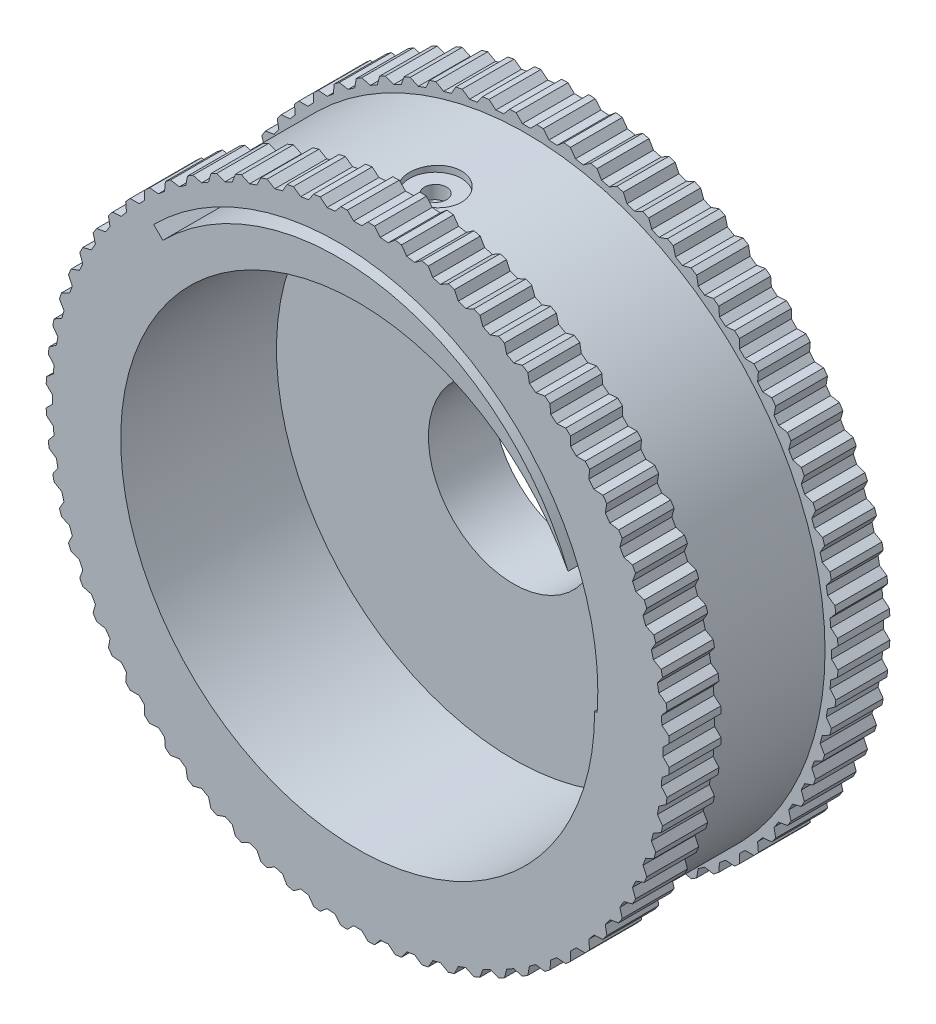
SolidWorks part; units mm, degrees
ref_plane "Front Plane" through (0, 0, 0) normal (0, 0, 1) x (1, 0, 0)
ref_plane "Top Plane" through (0, 0, 0) normal (0, 1, 0) x (1, 0, 0)
ref_plane "Right Plane" through (0, 0, 0) normal (1, 0, 0) x (0, 0, -1)
sketch "Sketch1" plane through (0, 0, 0) normal (0, 0, 1) x (1, 0, 0)
  circle A0 centre (0, 0) radius 24
  circle A1 centre (0, 0) radius 6.55
  dimension "D1" = 48
  dimension "D2" = 13.1
extrude "Main" add sketch "Sketch1" along normal mid plane 17
sketch "Sketch2" plane through (0, 0, 8.5) normal (0, 0, 1) x (1, 0, 0)
  circle A0 centre (0, 0) radius 18.25
  dimension "D1" = 36.5
extrude "ForSpringHole" cut sketch "Sketch2" against normal blind 12
ref_axis "Axis1" through (0, 0, 18.9) along (0, 0, -1)
sketch "Sketch3" plane through (0, 0, 8.5) normal (0, 0, 1) x (1, 0, 0)
  line L1 (-0.7945, 23.9868) -> (-0.3076, 23.5)
  line L2 (0.3076, 23.5) -> (0.7945, 23.9868)
  line L3 (-0.7945, 23.9868) -> (0, 0) construction
  line L4 (-0.3076, 23.5) -> (0.0672, -0.4418) construction
  line L5 (-0.3076, 23.5) -> (0.3076, 23.5)
  line L6 (0, 23.5) -> (0.0672, -0.4418) construction
  circle A0 centre (0, 0) radius 24 construction
  arc A4 (0.7945, 23.9868) -> (-0.7945, 23.9868) centre (0, 23.5) ccw
  point P9 (0, 23.5)
  dimension "D1" = 1.5
  dimension "D2" = 23.5
  dimension "D3" = 135
  dimension "D4" = 1
extrude "Teeth" cut sketch "Sketch3" against normal through all
pattern_circular "TeethCircularPattern" count 72 every 5 about axis through (0, 0, 18.9) along (0, 0, -1) of "Teeth"
sketch "Sketch4" plane through (0, 0, 0) normal (0, 0, 1) x (1, 0, 0)
  circle A0 centre (0, 0) radius 23
  circle A1 centre (0, 0) radius 25
  dimension "D1" = 46
  dimension "D2" = 50
extrude "ReduceSurfaceContact" cut sketch "Sketch4" against normal mid plane 9
sketch "Sketch6" plane through (0, 0, 8.5) normal (0, 0, 1) x (1, 0, 0)
  line L0 (-15.7102, 15.5738) -> (-15, 14.8697)
  line L1 (-1.5, 1.5) -> (-1.5, 0) construction
  line L2 (-1.5, 0) -> (0, 0) construction
  line L3 (18.4498, 0.084) -> (18.2498, 0.0831)
  line L4 (2.882, 23.8263) -> (2.3546, 23.3838) construction
  arc A0 (-15.7102, 15.5738) -> (18.4498, 0.084) centre (-1.5, 1.5) cw
  arc A1 (-15, 14.8697) -> (16.2055, 8.393) centre (-1.5, 1.5) cw
  circle A2 centre (0, 0) radius 18.25 construction
  arc A4 (16.2055, 8.393) -> (18.2498, 0.0831) centre (0, 0) cw
  circle A5 centre (0, 0) radius 18.25 construction
  point P5 (18.4842, 2.8133)
  point P10 (18.1066, 3.7948)
  point P17 (18.3574, 3.8837)
  point P18 (-3.9801, 20.3626)
  dimension "D1" = 1.5
  dimension "D2" = 1.5
  dimension "D3" = 20
  dimension "D4" = 1
  dimension "D5" = 0.2
  dimension "D6" = 15
extrude "SpringHole" cut sketch "Sketch6" against normal up to surface (12 mm away) up to face at (6.55, 0, -3.5)
ref_plane "Plane1" through (0, 24, 0) normal (0, 1, 0) x (1, 0, 0)
sketch "Sketch7" plane through (0, 24, 0) normal (0, 1, 0) x (1, 0, 0)
  circle A0 centre (0, -2.5) radius 0.85
  point P3 (-4.3837, -11.0521)
  point P6 (0, 0)
  dimension "D1" = 1.7
  dimension "D2" = 2.5
extrude "SpringFixingHole" cut sketch "Sketch7" against normal blind 10
sketch "Sketch8" plane through (0, 24, 0) normal (0, 1, 0) x (1, 0, 0)
  circle A0 centre (0, -2.5) radius 2
  dimension "D1" = 4
extrude "HeadOfScrew" cut sketch "Sketch8" against normal blind 1.5
